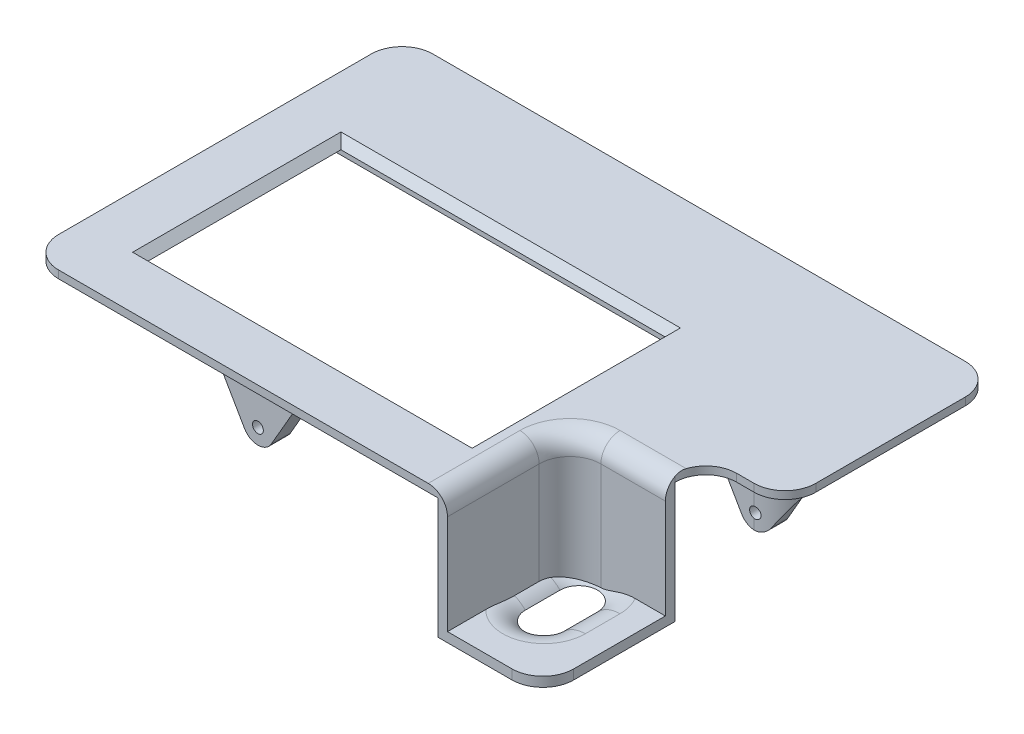
SolidWorks part; units mm, degrees
ref_plane "Front Plane" through (0, 0, 0) normal (0, 0, 1) x (1, 0, 0)
ref_plane "Top Plane" through (0, 0, 0) normal (0, 1, 0) x (1, 0, 0)
ref_plane "Right Plane" through (0, 0, 0) normal (1, 0, 0) x (0, 0, -1)
sketch "Sketch1" plane through (0, 0, 0) normal (0, 1, 0) x (1, 0, 0)
  line L0 (-77, 40.5) -> (-77, -40.5)
  line L1 (-69, -48.5) -> (29.28, -48.5)
  line L2 (29.28, -48.5) -> (29.28, -46)
  line L3 (29.28, -46) -> (-66.5, -46) construction
  line L4 (-74.5, -38) -> (-74.5, 38) construction
  line L5 (-66.5, 46) -> (66.5, 46) construction
  line L6 (74.5, 38) -> (74.5, 4.25) construction
  line L7 (66.5, -3.75) -> (62, -3.75) construction
  line L8 (54, -11.75) -> (54, -14.25) construction
  line L9 (54, -14.25) -> (56.5, -14.25)
  line L10 (64.5, -6.25) -> (69, -6.25)
  line L11 (77, 1.75) -> (77, 40.5)
  line L12 (69, 48.5) -> (-69, 48.5)
  line L13 (29.28, -46) -> (29.28, -14.25)
  line L14 (29.28, -14.25) -> (54, -14.25)
  arc A0 (-77, -40.5) -> (-69, -48.5) centre (-69, -40.5) ccw
  arc A1 (-74.5, -38) -> (-66.5, -46) centre (-66.5, -38) ccw construction
  arc A2 (-66.5, 46) -> (-74.5, 38) centre (-66.5, 38) ccw construction
  arc A3 (74.5, 38) -> (66.5, 46) centre (66.5, 38) ccw construction
  arc A4 (66.5, -3.75) -> (74.5, 4.25) centre (66.5, 4.25) ccw construction
  arc A5 (62, -3.75) -> (54, -11.75) centre (62, -11.75) ccw construction
  arc A6 (64.5, -6.25) -> (56.5, -14.25) centre (64.5, -14.25) ccw
  arc A7 (69, -6.25) -> (77, 1.75) centre (69, 1.75) ccw
  arc A8 (77, 40.5) -> (69, 48.5) centre (69, 40.5) ccw
  arc A9 (-69, 48.5) -> (-77, 40.5) centre (-69, 40.5) ccw
extrude "Boss-Extrude1" add sketch "Sketch1" along normal blind 2
sketch "Sketch2" plane through (0, 0, 0) normal (0, -1, 0) x (1, 0, 0)
  line L0 (54, 11.75) -> (54, 14.25) construction
  line L1 (66.5, 3.75) -> (62, 3.75) construction
  line L2 (74.5, -38) -> (74.5, -4.25) construction
  line L3 (-66.5, -46) -> (66.5, -46) construction
  line L4 (-74.5, 38) -> (-74.5, -38) construction
  line L5 (29.28, 46) -> (-66.5, 46) construction
  line L6 (54, 11.75) -> (54, 14.25)
  line L21 (66.5, 3.75) -> (62, 3.75)
  line L22 (74.5, -38) -> (74.5, -4.25)
  line L23 (-66.5, -46) -> (66.5, -46)
  line L24 (-74.5, 38) -> (-74.5, -38)
  line L25 (29.28, 46) -> (-66.5, 46)
  line L26 (29.28, 44) -> (-66.5, 44)
  line L27 (-72.5, 38) -> (-72.5, -38)
  line L28 (-66.5, -44) -> (66.5, -44)
  line L29 (72.5, -38) -> (72.5, -4.25)
  line L30 (66.5, 1.75) -> (62, 1.75)
  line L31 (52, 11.75) -> (52, 14.25)
  line L32 (29.28, 46) -> (29.28, 44)
  line L33 (54, 14.25) -> (52, 14.25)
  arc A0 (-74.5, -38) -> (-66.5, -46) centre (-66.5, -38) ccw construction
  arc A1 (54, 11.75) -> (62, 3.75) centre (62, 11.75) ccw construction
  arc A2 (74.5, -4.25) -> (66.5, 3.75) centre (66.5, -4.25) ccw construction
  arc A3 (66.5, -46) -> (74.5, -38) centre (66.5, -38) ccw construction
  arc A4 (-66.5, 46) -> (-74.5, 38) centre (-66.5, 38) ccw construction
  arc A15 (-74.5, -38) -> (-66.5, -46) centre (-66.5, -38) ccw
  arc A16 (54, 11.75) -> (62, 3.75) centre (62, 11.75) ccw
  arc A17 (74.5, -4.25) -> (66.5, 3.75) centre (66.5, -4.25) ccw
  arc A18 (66.5, -46) -> (74.5, -38) centre (66.5, -38) ccw
  arc A19 (-66.5, 46) -> (-74.5, 38) centre (-66.5, 38) ccw
  arc A20 (-66.5, 44) -> (-72.5, 38) centre (-66.5, 38) ccw
  arc A21 (-72.5, -38) -> (-66.5, -44) centre (-66.5, -38) ccw
  arc A22 (66.5, -44) -> (72.5, -38) centre (66.5, -38) ccw
  arc A23 (72.5, -4.25) -> (66.5, 1.75) centre (66.5, -4.25) ccw
  arc A24 (52, 11.75) -> (62, 1.75) centre (62, 11.75) ccw
  dimension "D1" = 2
extrude "Boss-Extrude2" add sketch "Sketch2" along normal blind 2
sketch "Sketch3" plane through (0, 0, 14.25) normal (0, 0, 1) x (1, 0, 0)
  line L0 (29.28, 2) -> (29.28, 0) construction
  line L5 (56.5, 2) -> (29.28, 2)
  line L6 (56.5, 2) -> (56.5, -31.28)
  line L7 (56.5, -31.28) -> (29.28, -31.28)
  line L8 (29.28, 2) -> (29.28, -31.28)
  dimension "D1" = 33.28
extrude "Boss-Extrude3" add sketch "Sketch3" along normal blind 2.5
sketch "Sketch4" plane through (29.28, 0, 0) normal (1, 0, 0) x (0, 0, -1)
  line L1 (-48.5, 2) -> (-16.75, 2)
  line L2 (-48.5, 2) -> (-48.5, -31.28)
  line L3 (-48.5, -31.28) -> (-16.75, -31.28)
  line L4 (-16.75, 2) -> (-16.75, -31.28)
extrude "Boss-Extrude4" add sketch "Sketch4" along normal blind 2.5
sketch "Sketch5" plane through (0, -31.28, 0) normal (0, -1, 0) x (1, 0, 0)
  line L0 (-69, 48.5) -> (29.28, 48.5) construction
  line L1 (29.28, 14.25) -> (56.5, 14.25)
  line L2 (29.28, 14.25) -> (29.28, 48.5)
  line L3 (29.28, 48.5) -> (56.5, 48.5)
  line L4 (56.5, 14.25) -> (56.5, 48.5)
  line L5 (56.5, 16.75) -> (56.5, 14.25) construction
extrude "Boss-Extrude5" add sketch "Sketch5" against normal blind 2.5
fillet "Fillet1" radius 8 1 edges at (56.5, -30.03, 48.5)
sketch "Sketch6" plane through (0, -28.78, 0) normal (0, 1, 0) x (1, 0, 0)
  line L0 (39.43, -22.12) -> (39.43, -31.12) construction
  line L1 (44.31, -22.12) -> (44.31, -31.12)
  line L2 (34.55, -22.12) -> (34.55, -31.12)
  line L3 (56.5, -16.75) -> (56.5, -40.5) construction
  line L4 (48.5, -48.5) -> (31.78, -48.5) construction
  arc A0 (44.31, -22.12) -> (34.55, -22.12) centre (39.43, -22.12) ccw
  arc A1 (34.55, -31.12) -> (44.31, -31.12) centre (39.43, -31.12) ccw
  point P2 (39.43, -26.62)
  dimension "D2" = 4.88
  dimension "D1" = 9
  dimension "D3" = 21.95
  dimension "D4" = 26.38
extrude "Cut-Extrude1" cut sketch "Sketch6" against normal up to next
fillet "Fillet3" radius 8 2 edges at (29.28, -15.64, 14.25) (31.78, -13.39, 16.75)
fillet "Fillet4" radius 8 3 edges at (39.43, -28.78, 36) (39.43, -28.78, 17.24) (44.31, -28.78, 26.62)
fillet "Fillet6" radius 5 3 edges at (31.78, 2, 36.625) (34.1231, 2, 19.0931) (48.14, 2, 16.75)
sketch "Sketch7" plane through (0, 0, 0) normal (0, -1, 0) x (1, 0, 0)
  line L0 (-77, -40.5) -> (-77, 40.5) construction
  line L1 (27.38, -21.88) -> (-69.62, -21.88)
  line L2 (27.38, -21.88) -> (27.38, 36.92)
  line L3 (27.38, 36.92) -> (-69.62, 36.92)
  line L4 (-69.62, -21.88) -> (-69.62, 36.92)
  line L5 (27.38, -21.88) -> (-69.62, 36.92) construction
  line L6 (27.38, 36.92) -> (-69.62, -21.88) construction
  line L7 (-69, 48.5) -> (29.28, 48.5) construction
  line L8 (-71.62, -23.88) -> (-71.62, 38.92)
  line L9 (29.38, 38.92) -> (-71.62, 38.92)
  line L10 (29.38, -23.88) -> (29.38, 38.92)
  line L11 (29.38, -23.88) -> (-71.62, -23.88)
  point P0 (-21.12, 7.52)
  dimension "D1" = 97
  dimension "D2" = 58.8
  dimension "D3" = 7.38
  dimension "D4" = 11.58
  dimension "D5" = 2
extrude "Boss-Extrude6" add sketch "Sketch7" along normal blind 6
sketch "Sketch8" plane through (0, 2, 0) normal (0, 1, 0) x (1, 0, 0)
  line L0 (-69, -48.5) -> (29.28, -48.5) construction
  line L1 (-61.42, 17.08) -> (22.58, 17.08)
  line L2 (-61.42, 17.08) -> (-61.42, -32.92)
  line L3 (-61.42, -32.92) -> (22.58, -32.92)
  line L4 (22.58, 17.08) -> (22.58, -32.92)
  line L5 (-61.42, 17.08) -> (22.58, -32.92) construction
  line L6 (-61.42, -32.92) -> (22.58, 17.08) construction
  line L7 (-77, 40.5) -> (-77, -40.5) construction
  point P0 (-19.42, -7.92)
  dimension "D1" = 50
  dimension "D2" = 84
  dimension "D3" = 15.58
  dimension "D4" = 15.58
extrude "Cut-Extrude2" cut sketch "Sketch8" against normal up to next
chamfer "Chamfer1" distance 2 angle 45 4 edges at (-19.42, 2, 32.92) (-61.42, 2, 7.92) (-19.42, 2, -17.08) (22.58, 2, 7.92)
sketch "Sketch9" plane through (0, 0, 48.5) normal (0, 0, 1) x (1, 0, 0)
  line L0 (-77, 2) -> (-77, 0) construction
  line L1 (-23.3241, -12) -> (-30.2523, 0)
  line L2 (-30.2523, 0) -> (-9.4677, 0)
  line L3 (69, 0) -> (-69, 0) construction
  line L4 (-9.4677, 0) -> (-16.3959, -12)
  circle A0 centre (-19.86, -10) radius 1.4
  arc A1 (-23.3241, -12) -> (-16.3959, -12) centre (-19.86, -10) ccw
  dimension "D1" = 2.8
  dimension "D2" = 8
  dimension "D3" = 57.14
  dimension "D4" = 10
  dimension "D5" = 60
extrude "Boss-Extrude7" add sketch "Sketch9" against normal blind 5 from surface separate body starting at face at (-18.61, -1, 46)
sketch "Sketch10" plane through (0, 0, 0) normal (0, 0, 1) x (1, 0, 0)
  line L1 (77, 0) -> (69, 0) construction
  line L2 (77, 2) -> (77, 0) construction
  line L3 (70.2141, -9) -> (75.4103, 0)
  line L4 (75.4103, 0) -> (58.0897, 0)
  line L5 (69, 0) -> (-69, 0) construction
  line L6 (58.0897, 0) -> (63.2859, -9)
  arc A0 (63.2859, -9) -> (70.2141, -9) centre (66.75, -7) ccw
  circle A1 centre (66.75, -7) radius 1.4
  dimension "D1" = 2.8
  dimension "D2" = 8
  dimension "D3" = 10.25
  dimension "D4" = 7
  dimension "D5" = 60
extrude "Boss-Extrude8" add sketch "Sketch10" against normal blind 5 from surface separate body starting at face at (64.25, -1, 3.75)
sketch "Sketch11" plane through (0, 0, -46) normal (0, 0, -1) x (-1, 0, 0)
  line L0 (-69, 0) -> (69, 0) construction
  line L1 (77, 2) -> (77, 0) construction
  line L2 (-77, 2) -> (-77, 0) construction
  line L3 (-65.4641, -9) -> (-70.6603, 0)
  line L5 (-70.6603, 0) -> (-53.3397, 0)
  line L6 (-53.3397, 0) -> (-58.5359, -9)
  line L7 (-69, 0) -> (-77, 0) construction
  line L8 (58.5359, -9) -> (53.3397, 0)
  line L12 (70.6603, 0) -> (65.4641, -9)
  line L13 (77, 0) -> (69, 0) construction
  line L14 (53.3397, 0) -> (70.6603, 0)
  circle A0 centre (-62, -7) radius 1.4
  circle A1 centre (62, -7) radius 1.4
  arc A2 (-65.4641, -9) -> (-58.5359, -9) centre (-62, -7) ccw
  arc A3 (58.5359, -9) -> (65.4641, -9) centre (62, -7) ccw
  dimension "D4" = 2.8
  dimension "D5" = 8
  dimension "D1" = 7
  dimension "D2" = 15
  dimension "D3" = 15
  dimension "D6" = 60
  dimension "D7" = 60
extrude "Boss-Extrude9" add sketch "Sketch11" against normal blind 5
sketch "Sketch12" plane through (0, 0, 0) normal (0, -1, 0) x (1, 0, 0)
  line L0 (-66.5, -46) -> (66.5, -46) construction
  line L1 (66.5, 3.75) -> (62, 3.75) construction
  line L2 (-66.5, -46) -> (66.5, -46)
  line L3 (66.5, 3.75) -> (62, 3.75)
  line L4 (54, 11.75) -> (84.2957, 11.75)
  line L5 (84.2957, 11.75) -> (84.2957, -4.25)
  line L6 (84.2957, -4.25) -> (74.5, -4.25)
  line L7 (74.5, -38) -> (84.2957, -38)
  line L8 (84.2957, -38) -> (84.2957, -62.9296)
  line L9 (84.2957, -62.9296) -> (-82.1257, -61.468)
  line L10 (-82.1257, -61.468) -> (-82.1257, -38)
  line L11 (-82.1257, -38) -> (-74.5, -38)
  arc A0 (66.5, -46) -> (74.5, -38) centre (66.5, -38) ccw construction
  arc A1 (-74.5, -38) -> (-66.5, -46) centre (-66.5, -38) ccw construction
  arc A2 (54, 11.75) -> (62, 3.75) centre (62, 11.75) ccw construction
  arc A3 (74.5, -4.25) -> (66.5, 3.75) centre (66.5, -4.25) ccw construction
  arc A4 (66.5, -46) -> (74.5, -38) centre (66.5, -38) ccw
  arc A5 (-74.5, -38) -> (-66.5, -46) centre (-66.5, -38) ccw
  arc A6 (54, 11.75) -> (62, 3.75) centre (62, 11.75) ccw
  arc A7 (74.5, -4.25) -> (66.5, 3.75) centre (66.5, -4.25) ccw
extrude "Cut-Extrude3" cut sketch "Sketch12" along normal through all
